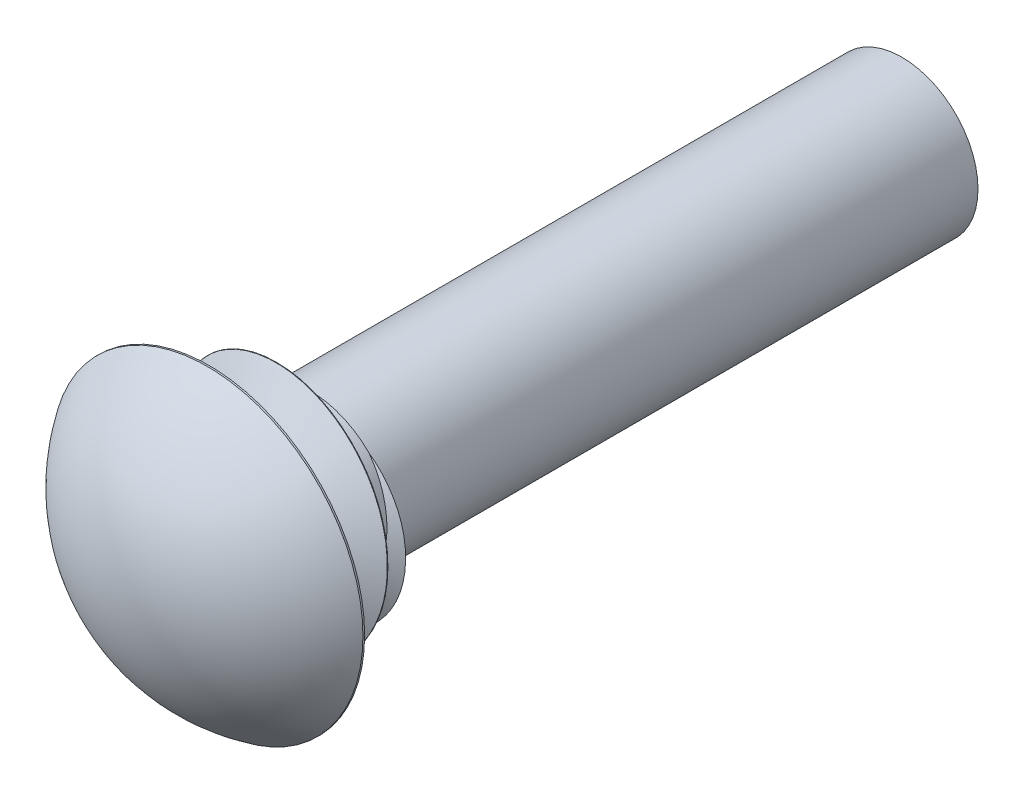
SolidWorks part; units mm, degrees
ref_plane "Front Plane" through (0, 0, 0) normal (0, 0, 1) x (1, 0, 0)
ref_plane "Top Plane" through (0, 0, 0) normal (0, 1, 0) x (1, 0, 0)
ref_plane "Right Plane" through (0, 0, 0) normal (1, 0, 0) x (0, 0, -1)
sketch "Sketch1" plane through (0, 0, 0) normal (0, 0, 1) x (1, 0, 0)
  circle A0 centre (0, 0) radius 1.7526
curve "Helix/Spiral1" pitch 0.7937 height 1.524 radius 1.7526 left hand yes centre (0, 0, 0) axis (0, 0, 1) start towards (0, 1, 0)
sketch "Sketch2" plane through (0, 0, 0) normal (0, 0, 1) x (1, 0, 0)
  circle A0 centre (0, 0) radius 1.7526
extrude "Boss-Extrude1" add sketch "Sketch2" along normal blind 1.524
sketch "Sketch3" plane through (0, 0, 0) normal (1, 0, 0) x (0, 0, -1)
  line L0 (-0.3925, 1.7526) -> (-0.0992, 1.2446)
  line L1 (-0.0992, 1.2446) -> (0.0992, 1.2446)
  line L2 (0.0992, 1.2446) -> (0.3925, 1.7526)
  line L3 (0.3925, 1.7526) -> (-0.3925, 1.7526)
  line L4 (0, 1.7526) -> (0, 1.2446) construction
  point P6 (0, 0)
  point P7 (0, 0)
  dimension "D1" = 60
  dimension "D2" = 0.508
  dimension "D3" = 0.1984
sweep "Cut-Sweep1" cut profiles "Sketch3" path "Helix/Spiral1" align with end faces yes
sketch "Sketch4" plane through (0, 0, 0) normal (0, 0, 1) x (1, 0, 0)
  circle A0 centre (0, 0) radius 1.143
extrude "Boss-Extrude2" add sketch "Sketch4" against normal blind 8.89
ref_plane "Plane1" through (0, 0, -4.445) normal (0, 0, -1) x (-1, 0, 0)
sketch "Sketch5" plane through (0, 0, 1.524) normal (0, 0, 1) x (1, 0, 0)
  circle A0 centre (0, 0) radius 2.34
extrude "Boss-Extrude3" add sketch "Sketch5" along normal blind 0.0254
dome "Dome1" faces to dome 1 distance 1.27 reverse direction no elliptical dome no face at (2.34, 0, 1.5494) parameters "D1"=1.27
